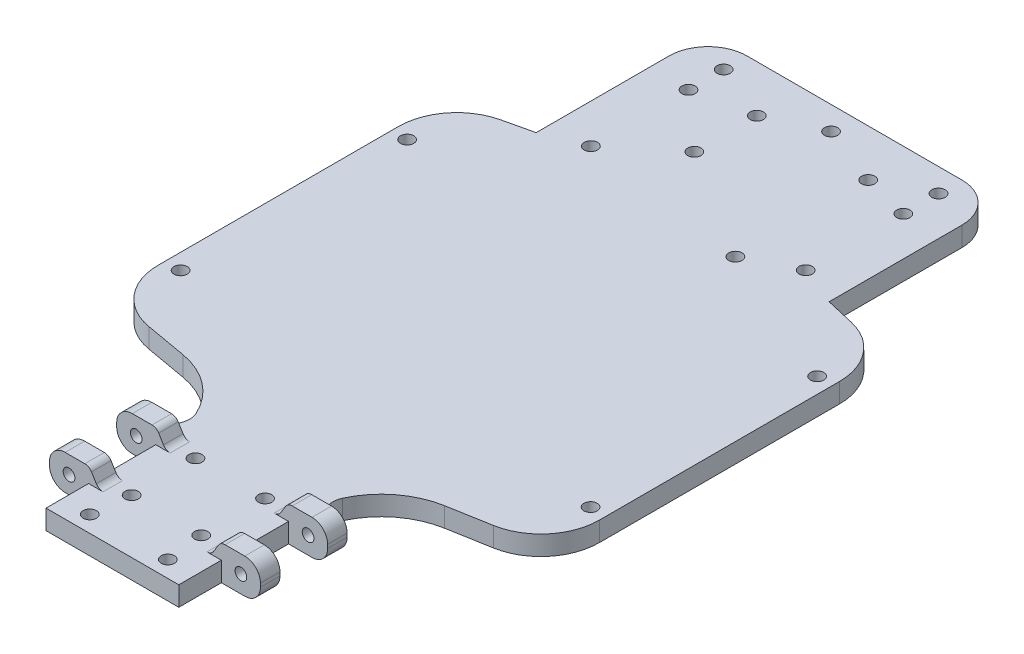
SolidWorks part; units mm, degrees
ref_plane "Plan de face" through (0, 0, 0) normal (0, 0, 1) x (1, 0, 0)
ref_plane "Plan de dessus" through (0, 0, 0) normal (0, 1, 0) x (1, 0, 0)
ref_plane "Plan de droite" through (0, 0, 0) normal (1, 0, 0) x (0, 0, -1)
sketch "Esquisse1" plane through (0, 0, 0) normal (0, 1, 0) x (1, 0, 0)
  line L0 (-33.922, -73) -> (33.922, -73) construction
  line L3 (-37.5, 95) -> (37.5, 95)
  line L4 (37.5, 51) -> (37.5, 95)
  line L5 (0, 0) -> (37.5, 95) construction
  line L6 (-21, -61.9) -> (-21, -66.9) construction
  line L7 (0, 95) -> (0, -95) construction
  line L8 (37.5, 51) -> (44.8743, 49.2975)
  line L9 (-24, -61.9) -> (-24, -66.9) construction
  line L10 (56.5, 34.682) -> (56.5, -26.8)
  line L11 (44.1047, -41.5721) -> (17, -46.3514)
  line L12 (22.5, -54.5324) -> (22.5, -84.1) construction
  line L13 (42.569, 51.5625) -> (42.569, 95.5625) construction
  line L14 (-8.1306, -79.1) -> (-42.569, -79.1) construction
  line L15 (56.5, -39.3865) -> (56.5, -125.6461) construction
  line L16 (-17, -95) -> (17, -95)
  line L17 (0, 0) -> (18.2122, -46.1377) construction
  line L18 (-56.5, 51) -> (56.5, 51) construction
  line L19 (-8.1306, -66.9) -> (-42.569, -66.9) construction
  line L20 (-33.922, -79.1) -> (-33.922, -66.9) construction
  line L24 (0, 0) -> (-18.2122, -46.1377) construction
  line L25 (-56.5, -39.3865) -> (-56.5, -125.6461) construction
  line L26 (33.922, -79.1) -> (33.922, -66.9) construction
  line L27 (8.1306, -66.9) -> (42.569, -66.9) construction
  line L28 (8.1306, -79.1) -> (42.569, -79.1) construction
  line L29 (17, -66.9) -> (27, -66.9)
  line L30 (27, -66.9) -> (27, -61.9)
  line L31 (27, -61.9) -> (17, -61.9)
  line L32 (24, -61.9) -> (24, -66.9) construction
  line L33 (21, -61.9) -> (21, -66.9) construction
  line L34 (27, -84.1) -> (17, -84.1)
  line L35 (17, -79.1) -> (27, -79.1)
  line L36 (27, -79.1) -> (27, -84.1)
  line L37 (17, -66.9) -> (17, -79.1)
  line L38 (17, -84.1) -> (17, -95)
  line L39 (17, -61.9) -> (17, -46.3514)
  line L40 (-42.569, 51.5625) -> (-42.569, 95.5625) construction
  line L41 (-22.5, -54.5324) -> (-22.5, -84.1) construction
  line L42 (0, 0) -> (-37.5, 95) construction
  line L44 (-17, -61.9) -> (-17, -46.3514)
  line L45 (-17, -84.1) -> (-17, -95)
  line L46 (-17, -66.9) -> (-17, -79.1)
  line L47 (-27, -79.1) -> (-27, -84.1)
  line L48 (-17, -79.1) -> (-27, -79.1)
  line L49 (-27, -84.1) -> (-17, -84.1)
  line L50 (-27, -61.9) -> (-17, -61.9)
  line L51 (-27, -66.9) -> (-27, -61.9)
  line L52 (-17, -66.9) -> (-27, -66.9)
  line L53 (-44.1047, -41.5721) -> (-17, -46.3514)
  line L54 (-56.5, 34.682) -> (-56.5, -26.8)
  line L55 (-37.5, 51) -> (-44.8743, 49.2975)
  line L56 (-37.5, 51) -> (-37.5, 95)
  arc A2 (56.5, -26.8) -> (44.1047, -41.5721) centre (41.5, -26.8) cw
  arc A3 (44.8743, 49.2975) -> (56.5, 34.682) centre (41.5, 34.682) cw
  arc A4 (-44.8743, 49.2975) -> (-56.5, 34.682) centre (-41.5, 34.682) ccw
  arc A5 (-56.5, -26.8) -> (-44.1047, -41.5721) centre (-41.5, -26.8) ccw
  point P0 (0, 0)
  point P16 (0, 51)
  point P33 (33.922, -73)
  point P52 (0, 51)
  point P53 (-56.5, 46.6135)
  point P62 (0, -73)
  point P69 (-33.922, -73)
  point P78 (56.5, 46.6135)
  point P87 (33.922, -73)
  point P88 (-33.922, -73)
  point P89 (56.5, 46.6135)
  dimension "D2" = 10
  dimension "D3" = 190
  dimension "D4" = 34
  dimension "D5" = 13
  dimension "D6" = 56.5
  dimension "D7" = 86
  dimension "D8" = 12.2
  dimension "D9" = 10
  dimension "D10" = 3
  dimension "D11" = 3
  dimension "D16" = 44
extrude "Boss.-Extru.1" add sketch "Esquisse1" along normal blind 5 contours L3 L4 L8 A3 L10 A2 L11 L39 L31 L30 L29 L37 L35 L36 L34 L38 L16 L45 L49 L47 L48 L46 L52 L51 L50 L44 L53 A5 L54 A4 L55 L56
fillet "Congé1" radius 20 2 edges at (17, 2.5, 46.3514) (-17, 2.5, 46.3514)
fillet "Congé2" radius 5 2 edges at (17, 2.5, 61.9) (-17, 2.5, 61.9)
sketch "Esquisse2" plane through (0, 0, 84.1) normal (0, 0, 1) x (1, 0, 0)
  line L0 (0, 17.1398) -> (0, -10.9487) construction
  line L1 (-27, 5) -> (-27, 8.9044)
  line L2 (-27, 8.9044) -> (-16.8331, 8.9044)
  line L3 (-16.8331, 8.9044) -> (-14.4276, 5)
  line L4 (-17, 5) -> (17, 5) construction
  line L6 (-17, 0) -> (17, 0) construction
  line L7 (-14.4276, 0) -> (-27, 0)
  line L8 (-27, 0) -> (-27, 5)
  line L9 (-14.4276, 5) -> (-14.4276, 0)
  line L10 (16.8331, 8.9044) -> (14.4276, 5)
  line L11 (27, 8.9044) -> (16.8331, 8.9044)
  line L12 (27, 5) -> (27, 8.9044)
  line L13 (27, 0) -> (27, 5)
  line L14 (14.4276, 0) -> (27, 0)
  line L15 (14.4276, 5) -> (14.4276, 0)
extrude "Boss.-Extru.2" add sketch "Esquisse2" against normal blind 5
ref_plane "Plan1" through (0, 0, 73) normal (0, 0, 1) x (1, 0, 0)
mirror "Symétrie1" about plane through (0, 0, 73) normal (0, 0, 1) of "Boss.-Extru.2"
fillet "Congé4" radius 2 8 edges at (-16.8331, 8.9044, 81.6) (-14.4276, 5, 81.6) (-16.8331, 8.9044, 64.4) (-14.4276, 5, 64.4) (16.8331, 8.9044, 64.4) (16.8331, 8.9044, 81.6) (14.4276, 5, 64.4) (14.4276, 5, 81.6)
fillet "Congé5" radius 4 8 edges at (-27, 8.9044, 81.6) (-27, 8.9044, 64.4) (27, 0, 64.4) (27, 0, 81.6) (27, 8.9044, 64.4) (27, 8.9044, 81.6) (-27, 0, 81.6) (-27, 0, 64.4)
sketch "Esquisse3" plane through (0, 0, 84.1) normal (0, 0, 1) x (1, 0, 0)
  line L0 (-27, 4.4522) -> (-17, 4.4522) construction
  line L3 (-22, 4.4522) -> (-22, 7.1928) construction
  line L4 (0, 9.9913) -> (0, -3.4658) construction
  circle A0 centre (-22, 4.4522) radius 1.5
  circle A1 centre (22, 4.4522) radius 1.5
  dimension "D1" = 3
extrude "Enlèv. mat.-Extru.2" cut sketch "Esquisse3" against normal blind 25
sketch "Esquisse4" plane through (0, 5, 0) normal (0, 1, 0) x (1, 0, 0)
  line L0 (-17, -90.8) -> (17, -90.8) construction
  line L2 (17, -84.1) -> (17, -95) construction
  line L3 (-17, -95) -> (17, -95) construction
  line L4 (-2.75, -73) -> (2.75, -73) construction
  line L5 (-8.9067, -81.172) -> (8.9067, -81.172)
  line L6 (-8.9067, -81.172) -> (-8.9067, -64.828)
  line L7 (-8.9067, -64.828) -> (8.9067, -64.828)
  line L8 (8.9067, -81.172) -> (8.9067, -64.828)
  line L9 (-8.9067, -81.172) -> (8.9067, -64.828) construction
  line L10 (-8.9067, -64.828) -> (8.9067, -81.172) construction
  line L11 (0, -87.4088) -> (0, -95) construction
  circle A0 centre (-10, -90.8) radius 1.7
  circle A1 centre (10, -90.8) radius 1.7
  circle A2 centre (8.9067, -64.828) radius 1.7
  circle A3 centre (8.9067, -81.172) radius 1.7
  circle A4 centre (-8.9067, -81.172) radius 1.7
  circle A5 centre (-8.9067, -64.828) radius 1.7
  point P12 (0, -73)
  dimension "D2" = 3.4
  dimension "D3" = 3.4
  dimension "D1" = 4.2
  dimension "D4" = 10
  dimension "D5" = 10
  dimension "D6" = 17.8135
  dimension "D7" = 16.344
extrude "Enlèv. mat.-Extru.3" cut sketch "Esquisse4" against normal blind 25 contours A4 | A3 | A2 | A5 | A0 | A1
sketch "Esquisse5" plane through (0, 5, 0) normal (0, 1, 0) x (1, 0, 0)
  line L0 (37.5, 51) -> (37.5, 95) construction
  line L1 (48.5019, 75) -> (-37.5, 75) construction
  line L2 (39.0019, 53) -> (58.0019, 53) construction
  line L3 (39.0019, 53) -> (39.0019, 97) construction
  line L4 (39.0019, 97) -> (58.0019, 97) construction
  line L5 (58.0019, 53) -> (58.0019, 97) construction
  line L6 (39.0019, 53) -> (58.0019, 97) construction
  line L7 (39.0019, 97) -> (58.0019, 53) construction
  line L8 (-37.5, 51) -> (-37.5, 95) construction
  line L9 (-37.5, 95) -> (37.5, 95) construction
  line L10 (15.5, 75) -> (15.5, 83) construction
  line L11 (27.5, 95) -> (27.5, 38.0482) construction
  line L12 (15.5, 75) -> (15.5, 49) construction
  line L13 (-27.5, 95) -> (-27.5, 53) construction
  line L14 (-13, 83) -> (-13, 67) construction
  line L15 (-13, 83) -> (15.5, 83) construction
  line L16 (-27.5, 89) -> (27.5, 89) construction
  circle A0 centre (15.5, 83) radius 1.7
  circle A1 centre (15.5, 49) radius 1.7
  circle A2 centre (-13, 83) radius 1.7
  circle A3 centre (-13, 67) radius 1.7
  circle A4 centre (27.5, 80) radius 1.7
  circle A5 centre (27.5, 55) radius 1.7
  circle A6 centre (27.5, 89) radius 1.7
  circle A7 centre (-27.5, 89) radius 1.7
  circle A8 centre (-27.5, 80) radius 1.7
  circle A9 centre (-27.5, 55) radius 1.7
  circle A10 centre (0, 89) radius 1.7
  point P3 (48.5019, 75)
  point P26 (-13, 75)
  dimension "D5" = 26
  dimension "D7" = 3.4
  dimension "D10" = 22
  dimension "D13" = 10
  dimension "D14" = 6
  dimension "D16" = 40
  dimension "D17" = 6
  dimension "D20" = 3.4
  dimension "D1" = 75
  dimension "D2" = 19
  dimension "D3" = 44
  dimension "D4" = 20
  dimension "D6" = 28.5
  dimension "D8" = 8
  dimension "D9" = 16
  dimension "D11" = 24.5
  dimension "D12" = 10
  dimension "D15" = 15
  dimension "D18" = 15
  dimension "D19" = 40
extrude "Enlèv. mat.-Extru.4" cut sketch "Esquisse5" against normal blind 10
sketch "Esquisse6" plane through (0, 5, 0) normal (0, 1, 0) x (1, 0, 0)
  line L0 (-52.4847, -25.059) -> (-52.4847, 32.941) construction
  line L1 (-56.5, 34.682) -> (-56.5, -26.8) construction
  line L2 (-56.5, 3.941) -> (56.5, 3.941) construction
  line L3 (56.5, 34.682) -> (56.5, -26.8) construction
  line L4 (0, 53.7621) -> (0, -51.3081) construction
  line L5 (52.4847, -25.059) -> (52.4847, 32.941) construction
  circle A0 centre (-52.4847, 32.941) radius 1.7
  circle A1 centre (-52.4847, -25.059) radius 1.7
  circle A2 centre (52.4847, -25.059) radius 1.7
  circle A3 centre (52.4847, 32.941) radius 1.7
  point P9 (-52.4847, 3.941)
  dimension "D2" = 3.4
  dimension "D1" = 58
extrude "Enlèv. mat.-Extru.5" cut sketch "Esquisse6" against normal blind 10
fillet "Congé6" radius 10 2 edges at (-37.5, 2.5, -95) (37.5, 2.5, -95)
